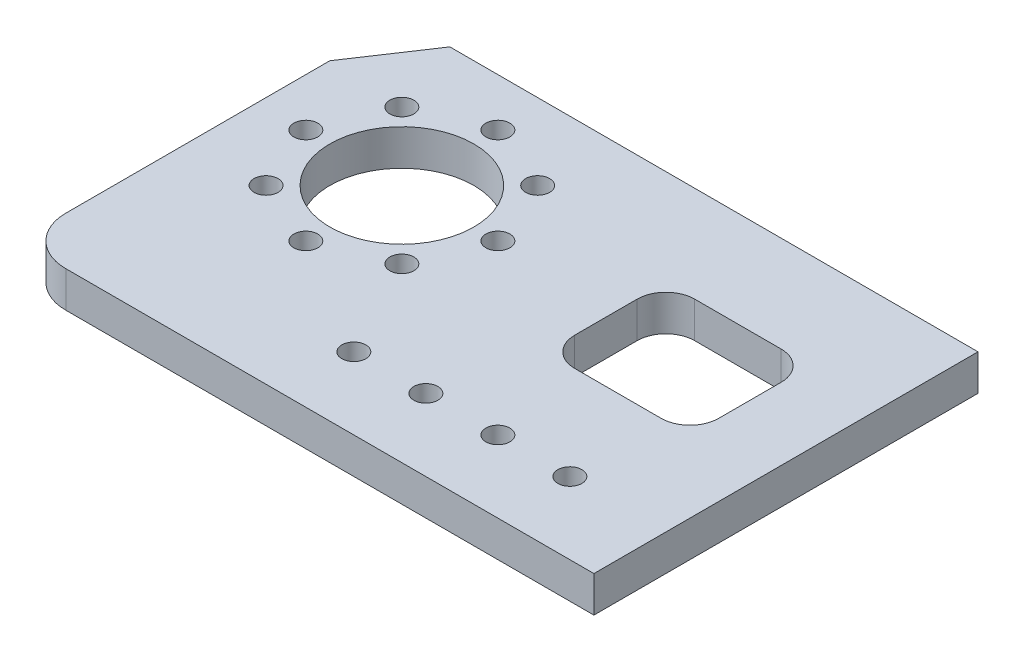
SolidWorks part; units mm, degrees
ref_plane "Front Plane" through (0, 0, 0) normal (0, 0, 1) x (1, 0, 0)
ref_plane "Top Plane" through (0, 0, 0) normal (0, 1, 0) x (1, 0, 0)
ref_plane "Right Plane" through (0, 0, 0) normal (1, 0, 0) x (0, 0, -1)
sketch "Sketch1" plane through (0, 0, 0) normal (0, 1, 0) x (1, 0, 0)
  line L0 (0, -19.05) -> (12.7, 0)
  line L1 (12.7, 0) -> (152.4, 0)
  line L2 (0, -19.05) -> (0, -88.9)
  line L3 (12.7, -101.6) -> (152.4, -101.6)
  line L4 (152.4, 0) -> (152.4, -101.6)
  line L6 (102.87, -25.4) -> (125.73, -25.4)
  line L7 (95.25, -33.02) -> (95.25, -49.53)
  line L8 (102.87, -57.15) -> (125.73, -57.15)
  line L9 (133.35, -33.02) -> (133.35, -49.53)
  circle A0 centre (38.1, -38.1) radius 19.05
  circle A1 centre (56.0605, -56.0605) radius 3.175
  arc A2 (0, -88.9) -> (12.7, -101.6) centre (12.7, -88.9) ccw
  circle A3 centre (38.1, -63.5) radius 3.175
  circle A4 centre (20.1395, -56.0605) radius 3.175
  circle A5 centre (12.7, -38.1) radius 3.175
  circle A6 centre (20.1395, -20.1395) radius 3.175
  circle A7 centre (38.1, -12.7) radius 3.175
  circle A8 centre (56.0605, -20.1395) radius 3.175
  circle A9 centre (63.5, -38.1) radius 3.175
  circle A10 centre (69.85, -82.55) radius 3.175
  circle A11 centre (88.9, -82.55) radius 3.175
  circle A12 centre (107.95, -82.55) radius 3.175
  circle A13 centre (127, -82.55) radius 3.175
  circle A14 centre (38.1, -38.1) radius 25.4 construction
  arc A15 (95.25, -49.53) -> (102.87, -57.15) centre (102.87, -49.53) ccw
  arc A16 (125.73, -57.15) -> (133.35, -49.53) centre (125.73, -49.53) ccw
  arc A17 (125.73, -25.4) -> (133.35, -33.02) centre (125.73, -33.02) cw
  arc A18 (102.87, -25.4) -> (95.25, -33.02) centre (102.87, -33.02) ccw
  dimension "D1" = 12.7
  dimension "D8" = 38.1
  dimension "D9" = 50.8
  dimension "D10" = 6.35
  dimension "D11" = 6.35
  dimension "D15" = 7.62
  dimension "D4" = 152.4
  dimension "D5" = 101.6
  dimension "D6" = 38.1
  dimension "D7" = 63.5
  dimension "D12" = 69.85
  dimension "D13" = 19.05
  dimension "D14" = 19.05
  dimension "D16" = 31.75
  dimension "D17" = 38.1
  dimension "D18" = 19.05
  dimension "D19" = 82.55
  dimension "D20" = 19.05
  dimension "D21" = 44.45
  dimension "D3" = 4
  dimension "D2" = 8
extrude "Boss-Extrude1" add sketch "Sketch1" along normal blind 9.525
